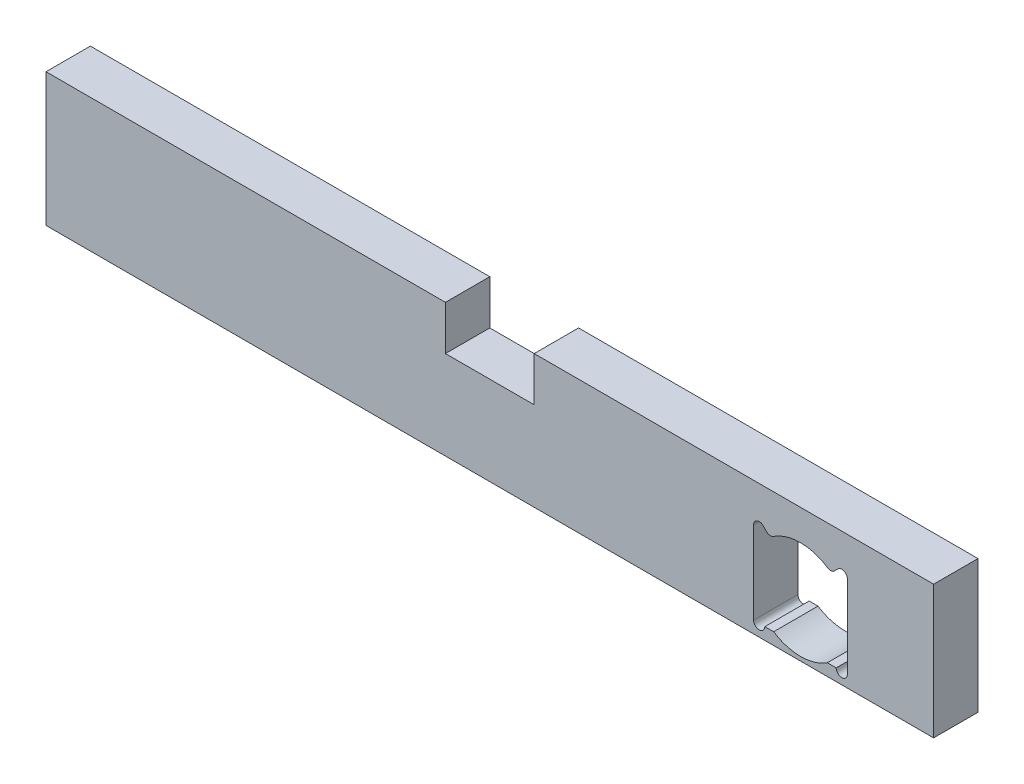
SolidWorks part; units mm, degrees
material "6061-T6 (SS)"
ref_plane "Front Plane" through (0, 0, 0) normal (0, 0, 1) x (1, 0, 0)
ref_plane "Top Plane" through (0, 0, 0) normal (0, 1, 0) x (1, 0, 0)
ref_plane "Right Plane" through (0, 0, 0) normal (1, 0, 0) x (0, 0, -1)
sketch "Sketch1" plane through (0, 0, 0) normal (0, 0, 1) x (1, 0, 0)
  line L1 (-215.9, -19.05) -> (38.1, -19.05)
  line L2 (-215.9, -19.05) -> (-215.9, 19.05)
  line L3 (-215.9, 19.05) -> (38.1, 19.05)
  line L4 (38.1, -19.05) -> (38.1, 19.05)
  line L5 (-215.9, -19.05) -> (38.1, 19.05) construction
  line L6 (-215.9, 19.05) -> (38.1, -19.05) construction
  line L7 (-215.9, 19.05) -> (38.1, 19.05)
  line L8 (-215.9, 19.05) -> (-215.9, -19.05)
  line L11 (-215.9, -19.05) -> (38.1, -19.05)
  line L12 (-215.9, -19.05) -> (-215.9, 19.05)
  line L15 (38.1, -19.05) -> (-215.9, -19.05)
  line L16 (38.1, -19.05) -> (38.1, 19.05)
  line L20 (38.1, -19.05) -> (38.1, 19.05)
  point P0 (0, 0)
  point P14 (-88.9, 0)
  dimension "D1" = 38.1
  dimension "D2" = 254
  dimension "D3" = 38.1
extrude "Boss-Extrude1" add sketch "Sketch1" along normal blind 12.7 contours L4 L3 L2 L1 region at (-88.9, 0, 0)
sketch "Sketch5" plane through (0, 0, 12.7) normal (0, 0, 1) x (1, 0, 0)
  line L0 (0, -3.81) -> (11.8187, 8.0087) construction
  line L1 (0, -3.81) -> (11.8187, -3.81) construction
  line L2 (0, -3.81) -> (0, 8.0087) construction
  line L3 (0, 8.0087) -> (11.8187, 8.0087) construction
  line L4 (11.8187, -3.81) -> (11.8187, 8.0087) construction
  line L5 (-10.6872, 9.1402) -> (-8.7721, 7.2252)
  line L6 (0, -3.81) -> (11.8187, -3.81) construction
  line L7 (0, -3.81) -> (0, -15.6287) construction
  line L8 (0, -15.6287) -> (11.8187, -15.6287) construction
  line L9 (11.8187, -3.81) -> (11.8187, -15.6287) construction
  line L10 (0, -3.81) -> (-11.8187, -3.81) construction
  line L11 (0, -3.81) -> (0, -15.6287) construction
  line L12 (0, -15.6287) -> (-11.8187, -15.6287) construction
  line L13 (-11.8187, -3.81) -> (-11.8187, -15.6287) construction
  line L14 (0, -3.81) -> (-11.8187, -3.81) construction
  line L15 (0, -3.81) -> (0, 8.0087) construction
  line L16 (0, 8.0087) -> (-11.8187, 8.0087) construction
  line L17 (-11.8187, -3.81) -> (-11.8187, 8.0087) construction
  line L18 (-13.4189, 8.0087) -> (-13.4189, -15.6287)
  line L19 (13.4189, 8.0087) -> (13.4189, -15.6287)
  line L20 (10.9269, 9.3374) -> (8.7958, 7.2063)
  line L21 (-13.4189, -15.6287) -> (-13.4189, -19.05)
  line L22 (-215.9, -19.05) -> (38.1, -19.05) construction
  line L23 (-13.4189, -19.05) -> (13.4189, -19.05)
  line L24 (13.4189, -19.05) -> (13.4189, -15.6287)
  line L25 (-10.2185, -15.6287) -> (-7.6839, -15.6287)
  line L26 (10.2185, -15.6287) -> (7.6839, -15.6287)
  circle A0 centre (0, -3.81) radius 14.097 construction
  circle A1 centre (11.8187, 8.0087) radius 1.6002
  circle A2 centre (-11.8187, 8.0087) radius 1.6002
  circle A3 centre (-11.8187, -15.6287) radius 1.6002
  circle A4 centre (11.8187, -15.6287) radius 1.6002
  arc A5 (-8.7721, 7.2252) -> (8.7958, 7.2063) centre (0, -3.81) cw
  arc A6 (-7.6839, -15.6287) -> (7.6839, -15.6287) centre (0, -3.81) ccw
  point P6 (9.9681, 6.1581)
  point P7 (10.6872, 6.8772)
  line M8 (-215.9, -19.05) -> (38.1, -19.05)
  dimension "D1" = 28.194
  dimension "D2" = 3.2004
  dimension "D3" = 1.017
  dimension "D4" = 45
  dimension "D5" = 45
  dimension "D6" = 15.24
extrude "Cut-Extrude4" cut sketch "Sketch5" against normal through all contours A5 L5 A2 L18 A3 L21 L24 A4 L19 A1 L20 M8 | A4 | A3 | A2 | A1 L20 region at (-0.0011, -3.8263, 12.7) region at (-11.8187, 8.0087, 12.7) region at (-11.8187, -15.6287, 12.7) region at (11.8205, 8.007, 12.7) region at (11.8187, -15.6287, 12.7)
fillet "Fillet1" radius 1.5875 2 edges at (8.7958, 7.2063, 6.35) (-8.7721, 7.2252, 6.35)
sketch "Sketch6" plane through (0, 0, 12.7) normal (0, 0, 1) x (1, 0, 0)
  line L0 (-215.9, 19.05) -> (38.1, 19.05) construction
  line L1 (-101.6, 19.05) -> (-76.2, 19.05)
  line L2 (-101.6, 19.05) -> (-101.6, 6.35)
  line L3 (-101.6, 6.35) -> (-76.2, 6.35)
  line L4 (-76.2, 19.05) -> (-76.2, 6.35)
  point P6 (-88.9, 6.35)
  point P7 (-88.9, 19.05)
  point P8 (-101.6, 19.05)
  point P9 (0, 0)
  point P10 (0, 0)
  dimension "D1" = 12.7
  dimension "D2" = 25.4
  dimension "D3" = 0
extrude "Cut-Extrude5" cut sketch "Sketch6" against normal through all
